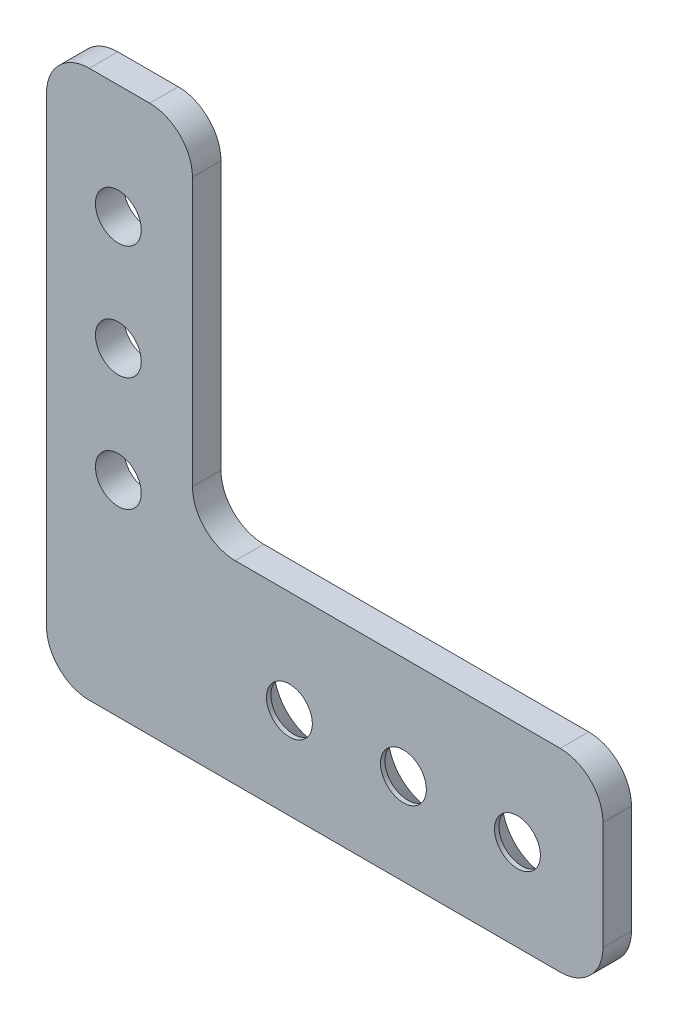
SolidWorks part; units mm, degrees
material "6061-T6 (SS)"
ref_plane "Front Plane" through (0, 0, 0) normal (0, 0, 1) x (1, 0, 0)
ref_plane "Top Plane" through (0, 0, 0) normal (0, 1, 0) x (1, 0, 0)
ref_plane "Right Plane" through (0, 0, 0) normal (1, 0, 0) x (0, 0, -1)
sketch "Sketch1" plane through (0, 0, 0) normal (0, 0, 1) x (1, 0, 0)
  line L0 (34.925, -19.05) -> (-27.051, -19.05) construction
  line L1 (-34.925, -31.75) -> (34.925, -31.75)
  line L2 (-34.925, -31.75) -> (-34.925, 31.75)
  line L3 (-34.925, 31.75) -> (34.925, 31.75)
  line L4 (34.925, -31.75) -> (34.925, 31.75)
  line L5 (-34.925, -31.75) -> (34.925, 31.75) construction
  line L6 (-34.925, 31.75) -> (34.925, -31.75) construction
  line L7 (34.925, 31.75) -> (-10.795, 31.75)
  line L8 (34.925, 31.75) -> (34.925, -7.62)
  line L9 (34.925, -7.62) -> (-10.795, -7.62)
  line L10 (-10.795, 31.75) -> (-10.795, -7.62)
  line L11 (-34.925, -31.75) -> (-27.051, -31.75)
  line L12 (-34.925, -31.75) -> (-34.925, 31.75)
  line L13 (-34.925, 31.75) -> (-27.051, 31.75)
  line L14 (-27.051, -31.75) -> (-27.051, 31.75)
  line L15 (-27.051, -31.75) -> (34.925, -31.75)
  line L16 (-27.051, -31.75) -> (-27.051, -29.21)
  line L17 (-27.051, -29.21) -> (34.925, -29.21)
  line L18 (34.925, -31.75) -> (34.925, -29.21)
  circle A0 centre (-19.05, -19.05) radius 2.5527
  circle A1 centre (-19.05, -6.35) radius 2.5527
  circle A2 centre (-19.05, 6.35) radius 2.5527
  circle A3 centre (-19.05, 19.05) radius 2.5527
  point P0 (0, 0)
  point P22 (25.4, -19.05)
  point P23 (0, -19.05)
  point P24 (12.7, -19.05)
  point P25 (0, 0)
  dimension "D7" = 5.1054
  dimension "D1" = 69.85
  dimension "D2" = 63.5
  dimension "D3" = 24.13
  dimension "D4" = 24.13
  dimension "D5" = 7.874
  dimension "D6" = 63.5
  dimension "D8" = 15.875
  dimension "D9" = 12.7
  dimension "D10" = 12.7
  dimension "D11" = 12.7
  dimension "D12" = 12.7
  dimension "D13" = 12.7
  dimension "D14" = 12.7
  dimension "D15" = 27.051
  dimension "D16" = 2.54
extrude "Boss-Extrude1" add sketch "Sketch1" along normal blind 3.175 contours L14 L17 L4 L9 L10 L3 A3 A2 A1 A0 | A0 region at (-2.786, -8.9226, 0) region at (-19.05, -19.05, 0)
fillet "Fillet1" radius 4.7625 6 edges at (-27.051, 31.75, 1.5875) (-10.795, 31.75, 1.5875) (-10.795, -7.62, 1.5875) (34.925, -7.62, 1.5875) (34.925, -29.21, 1.5875) (-27.051, -29.21, 1.5875)
hole_wizard "CSK for #10 Flat Head Machine Screw3" positions "Sketch6" profile "Sketch7" countersink size "#10" standard "ANSI Inch" end condition through all
sketch "Sketch6" plane through (0, 0, 0) normal (0, 0, -1) x (-1, 0, 0)
  point P0 (-25.4, -19.05)
  point P3 (-12.7, -19.05)
  point P6 (0, -19.05)
sketch "Sketch7" plane through (25.4, -19.05, 0) normal (1, 0, 0) x (0, 1, 0)
  line L0 (0, 0) -> (0, 3.175)
  line L1 (0, 3.175) -> (2.5527, 3.175)
  line L2 (2.5527, 3.175) -> (2.5527, 2.6882)
  line L3 (2.5527, 2.6882) -> (4.8895, 0)
  line L5 (4.8895, 0) -> (0, 0)
  line L6 (-2.5527, 2.6882) -> (-4.8895, 0) construction
  line L11 (0, -6.35) -> (0, 107.95) construction
  dimension "Thru Hole Dia." = 5.1054
  dimension "Thru Hole Depth" = 3.175
  dimension "Near C'Sink Dia." = 9.779
  dimension "Near C'Sink Angle" = 82
